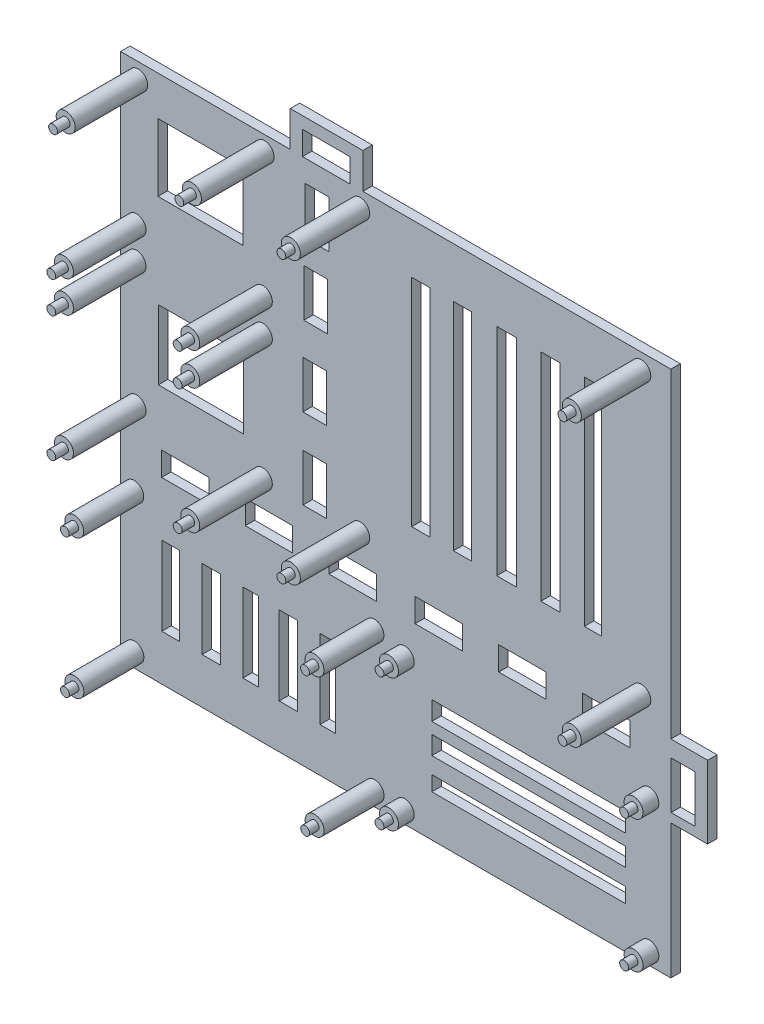
SolidWorks part; units mm, degrees
ref_plane "Front" through (0, 0, 0) normal (0, 0, 1) x (1, 0, 0)
ref_plane "Top" through (0, 0, 0) normal (0, 1, 0) x (1, 0, 0)
ref_plane "Right" through (0, 0, 0) normal (1, 0, 0) x (0, 0, -1)
sketch "Sketch1" plane through (0, 0, 0) normal (0, 0, 1) x (1, 0, 0)
  line L0 (100.4991, -43.0008) -> (107.9991, -43.0008)
  line L1 (-73.8486, 63.5813) -> (100.4132, 63.5813)
  line L2 (-73.8486, 63.5813) -> (-73.8486, -103.4187)
  line L3 (-73.8486, -103.4187) -> (100.4132, -103.4187)
  line L4 (100.4132, 63.5813) -> (100.4132, -103.4187)
  line L5 (18.3623, -20.6577) -> (18.3623, 47.7484)
  line L6 (18.3623, -20.6577) -> (24.1315, -20.6577)
  line L7 (24.1315, -20.6577) -> (24.1315, 47.7484)
  line L8 (18.3623, 47.7484) -> (24.1315, 47.7484)
  line L9 (31.5491, -20.6577) -> (31.5491, 47.7484)
  line L10 (31.5491, -20.6577) -> (37.3182, -20.6577)
  line L11 (37.3182, -20.6577) -> (37.3182, 47.7484)
  line L12 (31.5491, 47.7484) -> (37.3182, 47.7484)
  line L13 (45.2852, -20.6577) -> (45.2852, 47.7484)
  line L14 (45.2852, -20.6577) -> (51.6039, -20.6577)
  line L15 (51.6039, -20.6577) -> (51.6039, 47.7484)
  line L16 (45.2852, 47.7484) -> (51.6039, 47.7484)
  line L17 (59.2327, -20.6577) -> (59.2327, 47.7484)
  line L18 (59.2327, -20.6577) -> (65.34, -20.6577)
  line L19 (65.34, -20.6577) -> (65.34, 47.7484)
  line L20 (59.2327, 47.7484) -> (65.34, 47.7484)
  line L21 (73.0323, -20.6577) -> (73.0323, 47.7484)
  line L22 (73.0323, -20.6577) -> (78.5267, -20.6577)
  line L23 (78.5267, -20.6577) -> (78.5267, 47.7484)
  line L24 (73.0323, 47.7484) -> (78.5267, 47.7484)
  line L49 (-30.2062, -63.9161) -> (-30.2062, -88.9161)
  line L50 (-30.2062, -63.9161) -> (-35.1263, -63.9161)
  line L51 (-35.1263, -63.9161) -> (-35.1263, -88.9161)
  line L52 (-30.2062, -88.9161) -> (-35.1263, -88.9161)
  line L53 (-42.1988, -63.9161) -> (-42.1988, -88.9161)
  line L54 (-42.1988, -63.9161) -> (-48.0413, -63.9161)
  line L55 (-48.0413, -63.9161) -> (-48.0413, -88.9161)
  line L56 (-42.1988, -88.9161) -> (-48.0413, -88.9161)
  line L57 (-55.1138, -63.9161) -> (-55.1138, -88.9161)
  line L58 (-55.1138, -63.9161) -> (-60.8026, -63.9161)
  line L59 (-60.8026, -63.9161) -> (-60.8026, -88.9161)
  line L60 (-55.1138, -88.9161) -> (-60.8026, -88.9161)
  line L61 (24.7177, -64.8984) -> (86.0518, -64.8984)
  line L62 (24.7177, -64.8984) -> (24.7177, -70.8731)
  line L63 (24.7177, -70.8731) -> (86.0518, -70.8731)
  line L64 (86.0518, -64.8984) -> (86.0518, -70.8731)
  line L65 (24.7177, -74.4309) -> (86.0518, -74.4309)
  line L66 (24.7177, -74.4309) -> (24.7177, -80.2734)
  line L67 (24.7177, -80.2734) -> (86.0518, -80.2734)
  line L68 (86.0518, -74.4309) -> (86.0518, -80.2734)
  line L69 (24.7177, -85.4856) -> (86.0518, -85.4856)
  line L70 (24.7177, -85.4856) -> (24.7177, -90.1903)
  line L71 (24.7177, -90.1903) -> (86.0518, -90.1903)
  line L72 (86.0518, -85.4856) -> (86.0518, -90.1903)
  line L73 (-16.1164, 8.5813) -> (-8.6164, 8.5813)
  line L74 (-16.1164, 8.5813) -> (-16.1164, -6.4187)
  line L75 (-16.1164, -6.4187) -> (-8.6164, -6.4187)
  line L76 (-8.6164, 8.5813) -> (-8.6164, -6.4187)
  line L77 (100.4991, -43.0008) -> (100.4991, -58.0008)
  line L78 (100.4991, -58.0008) -> (107.9991, -58.0008)
  line L79 (107.9991, -43.0008) -> (107.9991, -58.0008)
  line L80 (-16.2551, 71.0423) -> (-1.2551, 71.0423)
  line L81 (100.4132, -37.8588) -> (112.0705, -37.8588)
  line L82 (100.4132, -37.8588) -> (100.4132, -60.8588)
  line L83 (100.4132, -60.8588) -> (112.0705, -60.8588)
  line L84 (112.0705, -37.8588) -> (112.0705, -60.8588)
  line L85 (-16.2551, 71.0423) -> (-16.2551, 63.5423)
  line L86 (-16.2551, 63.5423) -> (-1.2551, 63.5423)
  line L87 (-1.2551, 71.0423) -> (-1.2551, 63.5423)
  line L88 (-15.8365, 33.8761) -> (-8.3365, 33.8761)
  line L89 (-20.1164, 63.5813) -> (2.8836, 63.5813)
  line L90 (-20.1164, 63.5813) -> (-20.1164, 74.7916)
  line L91 (-20.1164, 74.7916) -> (2.8836, 74.7916)
  line L92 (2.8836, 63.5813) -> (2.8836, 74.7916)
  line L93 (-15.8365, 33.8761) -> (-15.8365, 18.8761)
  line L94 (-15.8365, 18.8761) -> (-8.3365, 18.8761)
  line L95 (-8.3365, 33.8761) -> (-8.3365, 18.8761)
  line L96 (-15.3863, 56.6293) -> (-7.8863, 56.6293)
  line L97 (-15.3863, 56.6293) -> (-15.3863, 41.6293)
  line L98 (-15.3863, 41.6293) -> (-7.8863, 41.6293)
  line L99 (-7.8863, 56.6293) -> (-7.8863, 41.6293)
  line L100 (-16.0783, -16.9285) -> (-8.5783, -16.9285)
  line L101 (-16.0783, -16.9285) -> (-16.0783, -31.9285)
  line L102 (-16.0783, -31.9285) -> (-8.5783, -31.9285)
  line L103 (-8.5783, -16.9285) -> (-8.5783, -31.9285)
  line L104 (-60.8486, -39.2508) -> (-45.8486, -39.2508)
  line L105 (-60.8486, -39.2508) -> (-60.8486, -46.7508)
  line L106 (-60.8486, -46.7508) -> (-45.8486, -46.7508)
  line L107 (-45.8486, -39.2508) -> (-45.8486, -46.7508)
  line L108 (-34.3486, -39.2508) -> (-19.3486, -39.2508)
  line L109 (-34.3486, -39.2508) -> (-34.3486, -46.7508)
  line L110 (-34.3486, -46.7508) -> (-19.3486, -46.7508)
  line L111 (-19.3486, -39.2508) -> (-19.3486, -46.7508)
  line L112 (-7.8486, -39.2508) -> (7.1514, -39.2508)
  line L113 (-7.8486, -39.2508) -> (-7.8486, -46.7508)
  line L114 (-7.8486, -46.7508) -> (7.1514, -46.7508)
  line L115 (7.1514, -39.2508) -> (7.1514, -46.7508)
  line L116 (19.4132, -39.2508) -> (34.4132, -39.2508)
  line L117 (19.4132, -39.2508) -> (19.4132, -46.7508)
  line L118 (19.4132, -46.7508) -> (34.4132, -46.7508)
  line L119 (34.4132, -39.2508) -> (34.4132, -46.7508)
  line L120 (45.9132, -39.2508) -> (60.9132, -39.2508)
  line L121 (45.9132, -39.2508) -> (45.9132, -46.7508)
  line L122 (45.9132, -46.7508) -> (60.9132, -46.7508)
  line L123 (60.9132, -39.2508) -> (60.9132, -46.7508)
  line L124 (72.4132, -39.2508) -> (87.4132, -39.2508)
  line L125 (72.4132, -39.2508) -> (72.4132, -46.7508)
  line L126 (72.4132, -46.7508) -> (87.4132, -46.7508)
  line L127 (87.4132, -39.2508) -> (87.4132, -46.7508)
  line L128 (-5.7929, -64.4534) -> (-5.7929, -89.4534)
  line L129 (-61.9991, 51.108) -> (-35.0763, 51.108)
  line L130 (-61.9991, 51.108) -> (-61.9991, 29.7572)
  line L131 (-61.9991, 29.7572) -> (-35.0763, 29.7572)
  line L132 (-35.0763, 51.108) -> (-35.0763, 29.7572)
  line L133 (-61.8887, 0.1104) -> (-34.9658, 0.1104)
  line L134 (-61.8887, 0.1104) -> (-61.8887, -21.875)
  line L135 (-61.8887, -21.875) -> (-34.9658, -21.875)
  line L136 (-34.9658, 0.1104) -> (-34.9658, -21.875)
  line L137 (-5.7929, -64.4534) -> (-10.713, -64.4534)
  line L138 (-10.713, -64.4534) -> (-10.713, -89.4534)
  line L139 (-5.7929, -89.4534) -> (-10.713, -89.4534)
  line L140 (-17.7855, -64.4534) -> (-17.7855, -89.4534)
  line L141 (-17.7855, -64.4534) -> (-23.628, -64.4534)
  line L142 (-23.628, -64.4534) -> (-23.628, -89.4534)
  line L143 (-17.7855, -89.4534) -> (-23.628, -89.4534)
  circle A0 centre (91.0714, 58.5013) radius 3
  circle A1 centre (2.0714, 58.5013) radius 3
  circle A2 centre (2.0714, -30.4987) radius 3
  circle A3 centre (91.0714, -30.4987) radius 3
  circle A4 centre (93.6114, -99.3787) radius 3
  circle A5 centre (93.6114, -57.4687) radius 3
  circle A6 centre (16.1414, -57.4687) radius 3
  circle A7 centre (16.1414, -99.3787) radius 3
  circle A8 centre (6.6014, -98.9187) radius 3
  circle A9 centre (6.5562, -54.9187) radius 3
  circle A10 centre (-69.5238, -54.9187) radius 3
  circle A11 centre (-69.4786, -98.9187) radius 3
  circle A12 centre (-28.7886, -31.0808) radius 3
  circle A13 centre (-68.7886, -31.0808) radius 3
  circle A14 centre (-68.7886, 8.5813) radius 3
  circle A15 centre (-28.7886, 8.5813) radius 3
  circle A16 centre (-28.7886, 18.9192) radius 3
  circle A17 centre (-68.7886, 18.5813) radius 3
  circle A18 centre (-68.2486, 58.5813) radius 3
  circle A19 centre (-28.2486, 58.9192) radius 3
  circle A20 centre (91.0714, 58.5013) radius 1.4
  circle A21 centre (91.0714, -30.4987) radius 1.4
  circle A22 centre (2.0714, -30.4987) radius 1.4
  circle A23 centre (2.0714, 58.5013) radius 1.4
  circle A24 centre (93.6114, -57.4687) radius 1.4
  circle A25 centre (93.6114, -99.3787) radius 1.4
  circle A26 centre (16.1414, -99.3787) radius 1.4
  circle A27 centre (16.1414, -57.4687) radius 1.4
  circle A28 centre (6.5562, -54.9187) radius 1.4
  circle A29 centre (6.6014, -98.9187) radius 1.4
  circle A30 centre (-28.7886, -31.0808) radius 1.4
  circle A31 centre (-69.5238, -54.9187) radius 1.4
  circle A32 centre (-69.4786, -98.9187) radius 1.4
  circle A33 centre (-68.7886, -31.0808) radius 1.4
  circle A34 centre (-68.7886, 8.5813) radius 1.4
  circle A35 centre (-68.7886, 18.5813) radius 1.4
  circle A36 centre (-28.7886, 18.9192) radius 1.4
  circle A37 centre (-68.2486, 58.5813) radius 1.4
  circle A38 centre (-28.2486, 58.9192) radius 1.4
  circle A39 centre (-28.7886, 8.5813) radius 1.4
  dimension "D14" = 48.5
extrude "Boss-Extrude3" add sketch "Sketch1" along normal blind 3 contours L4 L1 L2 L3 A19 A18 A17 A16 A15 A14 A13 A12 A11 A10 A9 A8 A7 A6 A5 A4 A3 A2 A1 A0 L5 L8 | L84 L81 L4 L83 L0 L79 L78 L77 | L1 L92 L91 L90 L80 L87 L86 L85 region at (13.8464, -20.3102, 0) region at (-19.8605, 69.1865, 0) region at (100.439, -49.3588, 0)
extrude "Boss-Extrude4" add sketch "Sketch1<6>" along normal blind 26 contours A12 | A15 | A16 | A19 | A18 | A17 | A14 | A13
sketch "Sketch1<6>" plane through (0, 0, 0) normal (0, 0, 1) x (1, 0, 0) same geometry as "Sketch1"
extrude "Boss-Extrude5" add sketch "Sketch1<8>" along normal blind 22 contours A10 | A9 | A8 | A11
sketch "Sketch1<8>" plane through (0, 0, 0) normal (0, 0, 1) x (1, 0, 0) same geometry as "Sketch1"
extrude "Boss-Extrude6" add sketch "Sketch1<10>" along normal blind 8 contours A6 | A7 | A4 | A5
sketch "Sketch1<10>" plane through (0, 0, 0) normal (0, 0, 1) x (1, 0, 0) same geometry as "Sketch1"
extrude "Boss-Extrude7" add sketch "Sketch1<11>" along normal blind 25 contours A2 | A3 | A0 | A1
sketch "Sketch1<11>" plane through (0, 0, 0) normal (0, 0, 1) x (1, 0, 0) same geometry as "Sketch1"
extrude "Boss-Extrude8" add sketch "Sketch1<12>" along normal blind 30 contours A37 | A38 | A36 | A35 | A34 | A39 | A30 | A33
sketch "Sketch1<12>" plane through (0, 0, 0) normal (0, 0, 1) x (1, 0, 0) same geometry as "Sketch1"
extrude "Boss-Extrude9" add sketch "Sketch1<13>" along normal blind 25 contours A32 | A29 | A31 | A28 region at (6.6014, -98.9187, 0) region at (-69.4786, -98.9187, 0)
sketch "Sketch1<13>" plane through (0, 0, 0) normal (0, 0, 1) x (1, 0, 0) same geometry as "Sketch1"
extrude "Boss-Extrude10" add sketch "Sketch1<15>" along normal blind 11 contours A26 | A25 | A24 | A27 region at (93.6114, -57.4687, 0) region at (93.6114, -99.3787, 0) region at (16.1414, -99.3787, 0)
sketch "Sketch1<15>" plane through (0, 0, 0) normal (0, 0, 1) x (1, 0, 0) same geometry as "Sketch1"
extrude "Boss-Extrude11" add sketch "Sketch1<16>" along normal blind 28 contours A22 | A21 | A20 | A23
sketch "Sketch1<16>" plane through (0, 0, 0) normal (0, 0, 1) x (1, 0, 0) same geometry as "Sketch1"
